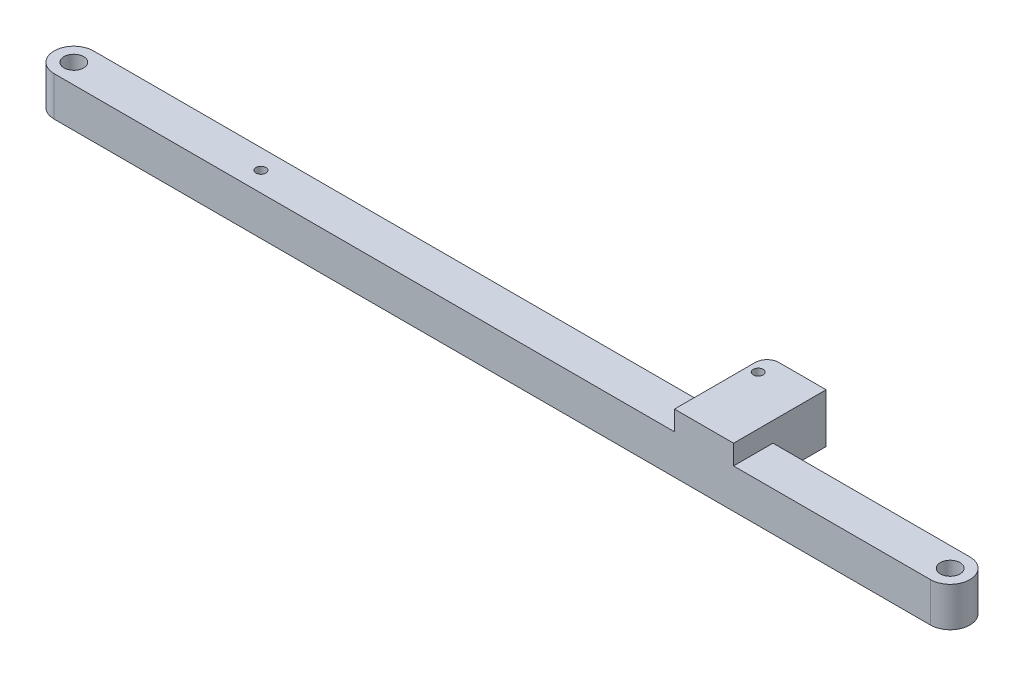
SolidWorks part; units mm, degrees
ref_plane "Front Plane" through (0, 0, 0) normal (0, 0, 1) x (1, 0, 0)
ref_plane "Top Plane" through (0, 0, 0) normal (0, 1, 0) x (1, 0, 0)
ref_plane "Right Plane" through (0, 0, 0) normal (1, 0, 0) x (0, 0, -1)
sketch "Sketch2" plane through (0, 0, 0) normal (0, 1, 0) x (1, 0, 0)
  line L0 (0, 0) -> (120.65, 0)
  line L1 (0, 0) -> (565.15, 0)
  line L2 (0, 0) -> (0, 25.4) construction
  line L3 (0, 25.4) -> (565.15, 25.4)
  line L4 (565.15, 0) -> (565.15, 25.4) construction
  line L5 (120.65, 0) -> (120.65, 25.4) construction
  circle A0 centre (120.65, 12.7) radius 12.7
  arc A1 (565.15, 25.4) -> (565.15, 0) centre (565.15, 12.7) cw
  circle A2 centre (120.65, 12.7) radius 3.175
  circle A3 centre (565.15, 12.7) radius 6.35
  arc A4 (0, 25.4) -> (0, 0) centre (0, 12.7) ccw
  circle A5 centre (0, 12.7) radius 6.35
  dimension "D4" = 6.35
  dimension "D5" = 12.7
  dimension "D6" = 12.7
  dimension "D1" = 565.15
  dimension "D2" = 25.4
  dimension "D3" = 120.65
extrude "Boss-Extrude1" add sketch "Sketch2" along normal blind 25.4 contours A0 L3 L2 L0 | A0 A2 | A1 L3 A0 L1 A3 region at (52.5215, 0, -12.7) region at (350.4658, 0, -12.7) region at (108.3092, 0, -12.7)
sketch "Sketch12" plane through (0, 0, -25.4) normal (0, 0, -1) x (-1, 0, 0)
  line L0 (-565.15, 25.4) -> (-438.15, 25.4)
  line L1 (0, 25.4) -> (-565.15, 25.4) construction
  line L2 (-438.15, 0) -> (-438.15, 38.1)
  line L3 (0, 0) -> (-565.15, 0) construction
  line L4 (-438.15, 38.1) -> (-400.05, 38.1)
  line L5 (-400.05, 38.1) -> (-400.05, 0)
  line L6 (-400.05, 0) -> (-438.15, 0)
  line L7 (-438.15, 6.35) -> (-400.05, 6.35)
  line L8 (-431.8, 12.7) -> (-400.05, 12.7)
  line L9 (-431.8, 31.75) -> (-400.05, 31.75)
  line L10 (-431.8, 12.7) -> (-431.8, 31.75)
  line M3 (0, 25.4) -> (-565.15, 25.4)
  dimension "D1" = 127
  dimension "D2" = 38.1
  dimension "D3" = 6.35
  dimension "D4" = 6.35
  dimension "D5" = 6.35
  dimension "D6" = 38.1
  dimension "D7" = 6.35
sketch "Sketch14" plane through (0, 25.4, 0) normal (0, 1, 0) x (1, 0, 0)
  line L0 (400.05, 25.4) -> (400.05, 0)
  line L1 (438.15, 25.4) -> (400.05, 25.4) construction
  line L2 (0, 0) -> (565.15, 0) construction
  line L3 (400.05, 0) -> (438.15, 0)
  line L4 (438.15, 0) -> (438.15, 25.4)
  line L5 (400.05, 25.4) -> (438.15, 25.4) construction
  line L6 (438.15, 25.4) -> (400.05, 25.4)
  line L7 (438.15, 25.4) -> (565.15, 25.4)
  line M2 (565.15, 25.4) -> (0, 25.4)
  line M4 (0, 0) -> (565.15, 0)
  dimension "D1" = 127
  dimension "D2" = 38.1
extrude "Boss-Extrude7" add sketch "Sketch12" along normal blind 44.45 contours L10 L9 L5 L4 L2 M3 | L8 L10 L2 L7 L5 M3 region at (423.0687, 11.9063, -25.4) region at (421.3679, 34.0179, -25.4)
sketch "Sketch15" plane through (0, 6.35, 0) normal (0, -1, 0) x (1, 0, 0)
  line L0 (400.05, -47.625) -> (406.4, -47.625) construction
  line L1 (400.05, -69.85) -> (400.05, -25.4) construction
  circle A0 centre (406.4, -47.625) radius 3.175
  dimension "D2" = 6.35
  dimension "D1" = 6.35
extrude "Cut-Extrude3" cut sketch "Sketch15" against normal through all contours A0
extrude "Boss-Extrude8" add sketch "Sketch14" along normal blind 12.7 contours L4 L0 M4 M2 region at (419.1, 25.4, -12.7)
sketch "Sketch17" plane through (0, 6.35, 0) normal (0, -1, 0) x (1, 0, 0)
  line L0 (400.05, -25.4) -> (400.05, -59.69)
  line L1 (400.05, -69.85) -> (400.05, -25.4) construction
  line L2 (400.05, -59.69) -> (438.15, -59.69)
  line L3 (438.15, -69.85) -> (438.15, -25.4) construction
  line L4 (438.15, -59.69) -> (438.15, -25.4)
  line L5 (438.15, -25.4) -> (400.05, -25.4)
  line M3 (400.05, -25.4) -> (400.05, -69.85)
  line M4 (400.05, -69.85) -> (438.15, -69.85)
  line M5 (438.15, -69.85) -> (438.15, -25.4)
  dimension "D1" = 34.29
extrude "Cut-Extrude4" cut sketch "Sketch17" against normal through all contours L2 M3 M4 M5 region at (419.1, 6.35, -64.77)
fillet "Fillet1" radius 7.62 2 edges at (400.05, 34.925, -59.69) (400.05, 9.525, -59.69)
